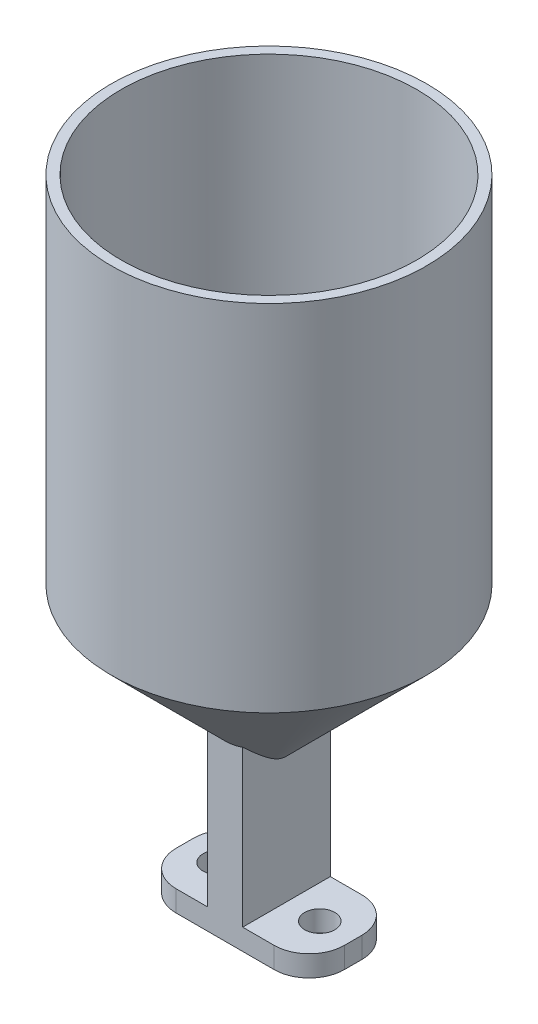
SolidWorks part; units mm, degrees
material "ABS"
ref_plane "Front Plane" through (0, 0, 0) normal (0, 0, 1) x (1, 0, 0)
ref_plane "Top Plane" through (0, 0, 0) normal (0, 1, 0) x (1, 0, 0)
ref_plane "Right Plane" through (0, 0, 0) normal (1, 0, 0) x (0, 0, -1)
sketch "Sketch1" plane through (0, 0, 0) normal (0, 1, 0) x (1, 0, 0)
  line L0 (-7.25, 0) -> (7.25, 0) construction
  line L2 (-2.5, -6.25) -> (2.5, -6.25) construction
  line L3 (-2.5, -6.25) -> (-2.5, 6.25) construction
  line L4 (-2.5, 6.25) -> (2.5, 6.25) construction
  line L5 (2.5, -6.25) -> (2.5, 6.25) construction
  line L6 (-2.5, -6.25) -> (2.5, 6.25) construction
  line L7 (-2.5, 6.25) -> (2.5, -6.25) construction
  line L8 (-7, -6.25) -> (7, -6.25)
  line L9 (-12, -1.25) -> (-12, 1.25)
  line L10 (-7, 6.25) -> (7, 6.25)
  line L11 (12, -1.25) -> (12, 1.25)
  line L12 (-12, -6.25) -> (12, 6.25) construction
  line L13 (-12, 6.25) -> (12, -6.25) construction
  circle A0 centre (-7.25, 0) radius 2.15
  circle A1 centre (7.25, 0) radius 2.15
  circle A2 centre (-7.25, 0) radius 4.75 construction
  circle A3 centre (7.25, 0) radius 4.75 construction
  arc A4 (-7, -6.25) -> (-12, -1.25) centre (-7, -1.25) cw
  arc A5 (7, -6.25) -> (12, -1.25) centre (7, -1.25) ccw
  arc A6 (7, 6.25) -> (12, 1.25) centre (7, 1.25) cw
  arc A7 (-12, 1.25) -> (-7, 6.25) centre (-7, 1.25) cw
  point P4 (0, 0)
  point P9 (0, 0)
  point P14 (0, 0)
  dimension "D1" = 4.3
  dimension "D3" = 9.5
  dimension "D5" = 5
  dimension "D2" = 14.5
  dimension "D4" = 12.5
extrude "Boss-Extrude1" add sketch "Sketch1" along normal mid plane 3
sketch "Sketch3" plane through (0, 0, 6.25) normal (0, 0, 1) x (1, 0, 0)
  line L0 (-7, 1.5) -> (7, 1.5) construction
  line L1 (-2.5, 21.5) -> (2.5, 21.5) construction
  line L2 (-2.5, 21.5) -> (-2.5, 1.5) construction
  line L3 (-2.5, 1.5) -> (2.5, 1.5) construction
  line L4 (2.5, 21.5) -> (2.5, 1.5) construction
  line L5 (-2.5, 21.5) -> (2.5, 1.5) construction
  line L6 (-2.5, 1.5) -> (2.5, 21.5) construction
  line L8 (-12, 1.5) -> (-12, -1.5) construction
  line L9 (-2.5, 1.5) -> (-12, 1.5) construction
  line L10 (-2.5, 21.5) -> (2.5, 21.5)
  line L11 (-4.5, 17) -> (-12, 17) construction
  line L12 (-4.5, 17) -> (-4.5, 21.5) construction
  line L13 (-4.5, 21.5) -> (-12, 21.5) construction
  line L14 (-12, 17) -> (-12, 21.5) construction
  line L15 (-4.5, 17) -> (-12, 21.5) construction
  line L16 (-4.5, 21.5) -> (-12, 17) construction
  line L17 (-2.5, 1.5) -> (-2.5, 21.5)
  line L18 (-2.5, 1.5) -> (-12, 1.5) construction
  line L19 (-2.5, 1.5) -> (-2.5, 6.5) construction
  line L20 (-2.5, 6.5) -> (-12, 6.5) construction
  line L21 (-12, 1.5) -> (-12, 6.5) construction
  line L22 (-2.5, 1.5) -> (-12, 6.5) construction
  line L23 (-2.5, 6.5) -> (-12, 1.5) construction
  line L24 (0, 0) -> (0, 32.0144) construction
  line L25 (2.5, 21.5) -> (2.5, 1.5)
  line L26 (2.5, 1.5) -> (-2.5, 1.5)
  point P0 (0, 11.5)
  point P7 (-8.25, 19.25)
  point P11 (-7.25, 4)
  point P13 (0, 21.5)
  dimension "D1" = 9.5
  dimension "D2" = 20
  dimension "D3" = 7.5
  dimension "D4" = 4.5
  dimension "D5" = 5
extrude "Boss-Extrude3" add sketch "Sketch3" against normal up to surface (12.5 mm away) up to face at (0, 0, -6.25)
sketch "Sketch4" plane through (0, 0, 0) normal (0, 0, 1) x (1, 0, 0)
  line L0 (-2.5, 19.5) -> (-22.5, 39.5)
  line L1 (-2.5, 1.5) -> (-2.5, 21.5) construction
  line L4 (-21.0858, 40.0858) -> (-22.0858, 39.0858) construction
  line L7 (-2.5, 21.5) -> (0, 21.5)
  line L8 (0, -200000) -> (0, 200032.0144) construction
  line L9 (-2.5, 19.5) -> (0, 19.5)
  line L11 (0, 0) -> (0, 34.2554) construction
  line L12 (-22.5, 39.5) -> (-22.5, 90.0858)
  line L13 (-22.5, 90.0858) -> (-21.0858, 90.0858)
  line L14 (-21.0858, 90.0858) -> (-21.0858, 40.0858)
  line L15 (-21.0858, 40.0858) -> (-2.5, 21.5)
  line L16 (0, 21.5) -> (0, 19.5)
  dimension "D1" = 45
  dimension "D2" = 45
  dimension "D4" = 50
revolve "Revolve1" add sketch "Sketch4" angle 360 about L11
sketch "Sketch5" plane through (0, 21.5, 0) normal (0, 1, 0) x (1, 0, 0)
  line L6 (2.5, -6.25) -> (2.5, -3.7417)
  line L7 (-2.5, -3.7417) -> (-2.5, -6.25)
  line L8 (-2.5, -6.25) -> (2.5, -6.25)
  line L9 (2.5, -6.25) -> (2.5, -3.7417)
  line L10 (-2.5, -3.7417) -> (-2.5, -6.25)
  line L11 (-2.5, -6.25) -> (2.5, -6.25)
  line L15 (-2.5, 6.25) -> (-2.5, 3.7417)
  line L16 (2.5, 3.7417) -> (2.5, 6.25)
  line L17 (2.5, 6.25) -> (-2.5, 6.25)
  line L18 (-2.5, 6.25) -> (-2.5, 3.7417)
  line L19 (2.5, 3.7417) -> (2.5, 6.25)
  line L20 (2.5, 6.25) -> (-2.5, 6.25)
  arc A2 (-2.5, -3.7417) -> (2.5, -3.7417) centre (0, 0) ccw
  arc A3 (-2.5, -3.7417) -> (2.5, -3.7417) centre (0, 0) ccw
  arc A5 (2.5, 3.7417) -> (-2.5, 3.7417) centre (0, 0) ccw
  arc A6 (2.5, 3.7417) -> (-2.5, 3.7417) centre (0, 0) ccw
  dimension "D1" = 0
  dimension "D2" = 0
extrude "Boss-Extrude4" add sketch "Sketch5" along normal up to next
